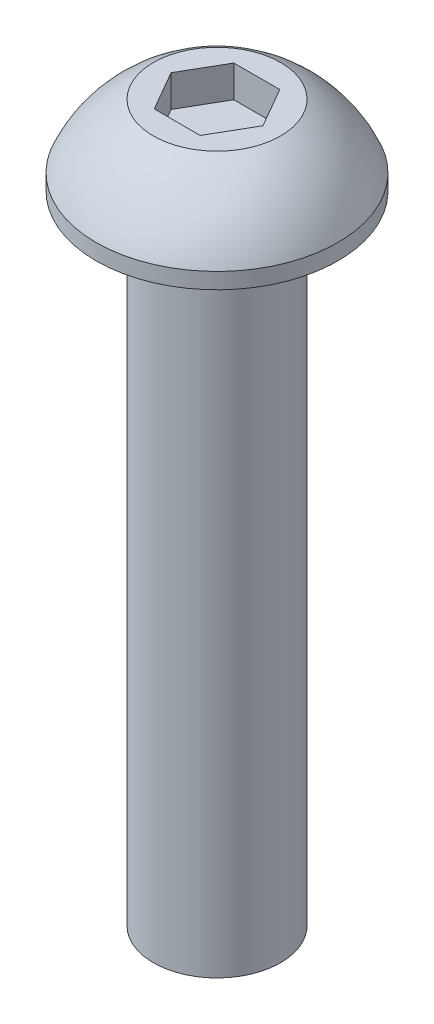
SolidWorks part; units mm, degrees
material "AISI 304"
ref_plane "Front Plane" through (0, 0, 0) normal (0, 0, 1) x (1, 0, 0)
ref_plane "Top Plane" through (0, 0, 0) normal (0, 1, 0) x (1, 0, 0)
ref_plane "Right Plane" through (0, 0, 0) normal (1, 0, 0) x (0, 0, -1)
sketch "Sketch1" plane through (0, 0, 0) normal (0, 0, 1) x (1, 0, 0)
  line L0 (2, 0) -> (3.8, 0)
  line L1 (3.8, 0) -> (3.8, 0.5)
  line L2 (2, 2.5) -> (0, 2.5)
  line L3 (2, 0) -> (2, -20)
  line L4 (2, -20) -> (0, -20)
  line L5 (0, -20) -> (0, 2.5)
  arc A0 (3.8, 0.5) -> (2, 2.5) centre (0.1, -1.02) ccw
  point P9 (0, 0)
  point P10 (0, 0)
  point P11 (1.6877, 0.3877)
  dimension "D5" = 4
  dimension "D1" = 2
  dimension "D2" = 20
  dimension "D3" = 3.8
  dimension "D4" = 2.5
  dimension "D6" = 2
  dimension "D7" = 0.5
revolve "Revolve1" add sketch "Sketch1" angle 360 about L5
sketch "Sketch2" plane through (0, 2.5, 0) normal (0, 1, 0) x (1, 0, 0)
  line L1 (0.7217, 1.25) -> (-0.7217, 1.25)
  line L2 (-0.7217, 1.25) -> (-1.4434, 0)
  line L3 (-1.4434, 0) -> (-0.7217, -1.25)
  line L4 (-0.7217, -1.25) -> (0.7217, -1.25)
  line L5 (0.7217, -1.25) -> (1.4434, 0)
  line L6 (1.4434, 0) -> (0.7217, 1.25)
  circle A0 centre (0, 0) radius 1.25 construction
  dimension "D1" = 2.5
extrude "Cut-Extrude1" cut sketch "Sketch2" against normal blind 1
